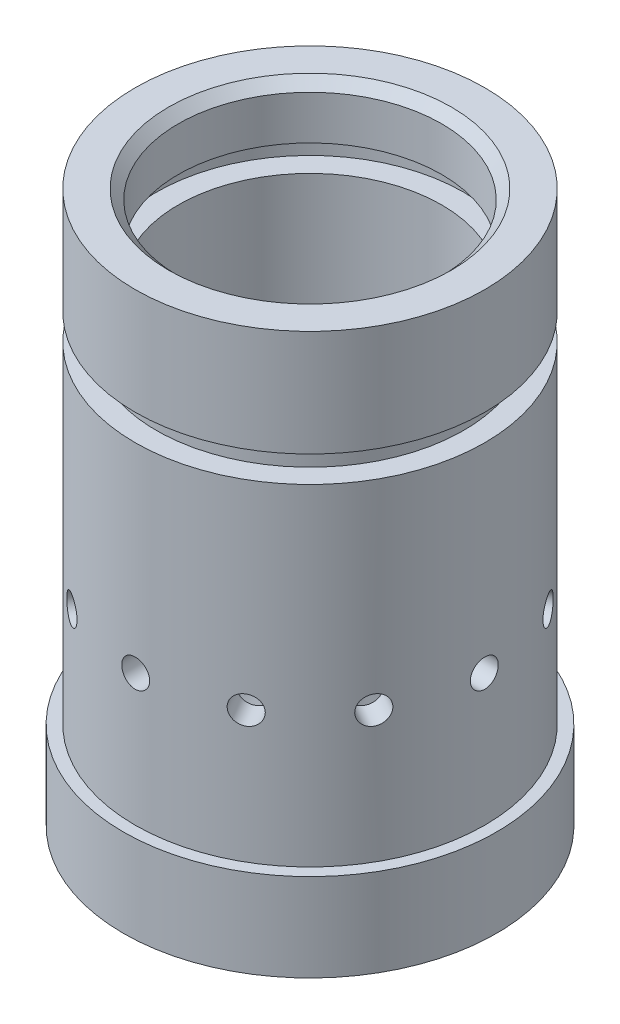
SolidWorks part; units mm, degrees
material "6061 Alloy"
ref_plane "Front Plane" through (0, 0, 0) normal (0, 0, 1) x (1, 0, 0)
ref_plane "Top Plane" through (0, 0, 0) normal (0, 1, 0) x (1, 0, 0)
ref_plane "Right Plane" through (0, 0, 0) normal (1, 0, 0) x (0, 0, -1)
sketch "Sketch1" plane through (0, 0, 0) normal (0, 0, 1) x (1, 0, 0)
  line L0 (0, 0) -> (0, 10.9165) construction
  line L1 (19.05, -48.1471) -> (19.05, -6.4911)
  line L2 (19.05, -6.4911) -> (20.447, -5.0941)
  line L3 (20.447, -5.0941) -> (25.2857, -5.0941)
  line L6 (25.2857, -5.0941) -> (25.2857, -48.1471)
  line L7 (25.2857, -48.1471) -> (19.05, -48.1471)
  line L8 (19.05, -48.1471) -> (15.875, -48.1471)
  line L9 (15.875, -48.1471) -> (25.7175, -84.8798)
  line L11 (25.7175, -84.8798) -> (26.9875, -84.8798)
  line L13 (15.875, -48.1471) -> (7.9375, -18.5239) construction
  line L14 (26.9875, -72.1798) -> (26.9875, -84.8798)
  line L15 (25.2857, -48.1471) -> (25.2857, -72.1798)
  line L16 (-26.9875, -72.1798) -> (26.9875, -72.1798) construction
  line L17 (25.2857, -72.1798) -> (26.9875, -72.1798)
  line L18 (-26.9875, -72.1798) -> (-26.9875, -84.8798)
  line L19 (-26.9875, -84.8798) -> (26.9875, -84.8798) construction
  line L20 (-22.2123, -5.0941) -> (22.2123, -5.0941) construction
  line L21 (19.05, -12.8411) -> (22.225, -12.8411)
  line L22 (25.2857, -20.4611) -> (22.225, -20.4611)
  line L23 (25.2857, -20.4611) -> (25.2857, -24.2711)
  line L24 (25.2857, -24.2711) -> (22.225, -24.2711)
  line L25 (22.225, -20.4611) -> (22.225, -24.2711)
  line L26 (19.05, -12.8411) -> (19.05, -16.6511)
  line L27 (19.05, -16.6511) -> (22.225, -16.6511)
  line L28 (22.225, -12.8411) -> (22.225, -16.6511)
  line L29 (-25.7175, -84.8798) -> (-26.9875, -84.8798)
  line L30 (-15.875, -48.1471) -> (-25.7175, -84.8798)
  line L31 (-22.225, -12.8411) -> (-22.225, -16.6511)
  line L32 (-19.05, -16.6511) -> (-22.225, -16.6511)
  line L33 (-19.05, -12.8411) -> (-19.05, -16.6511)
  line L34 (-22.225, -20.4611) -> (-22.225, -24.2711)
  line L35 (-25.2857, -24.2711) -> (-22.225, -24.2711)
  line L36 (-25.2857, -20.4611) -> (-25.2857, -24.2711)
  line L37 (-25.2857, -20.4611) -> (-22.225, -20.4611)
  line L38 (-19.05, -12.8411) -> (-22.225, -12.8411)
  line L39 (-25.2857, -72.1798) -> (-26.9875, -72.1798)
  line L40 (-25.2857, -48.1471) -> (-25.2857, -72.1798)
  line L41 (-19.05, -48.1471) -> (-15.875, -48.1471)
  line L42 (-25.2857, -48.1471) -> (-19.05, -48.1471)
  line L43 (-25.2857, -5.0941) -> (-25.2857, -48.1471)
  line L44 (-20.447, -5.0941) -> (-25.2857, -5.0941)
  line L45 (-19.05, -6.4911) -> (-20.447, -5.0941)
  line L46 (-19.05, -48.1471) -> (-19.05, -6.4911)
  point P26 (25.2857, -5.0941)
  point P37 (15.875, -48.1471)
  point P53 (-15.875, -48.1471)
  point P54 (-25.2857, -5.0941)
  dimension "D1" = 44.45
  dimension "D2" = 3.81
  dimension "D3" = 44.45
  dimension "D4" = 3.81
  dimension "D5" = 19.05
  dimension "D6" = 45
  dimension "D7" = 1.397
  dimension "D8" = 3.0607
  dimension "D9" = 6.35
revolve "Revolve1" add sketch "Sketch1" angle 360 about L0 region at (22.1785, -27.4978, 0) region at (22.6048, -61.9724, 0)
ref_plane "Plane1" through (0, 0, -25.2857) normal (0, 0, -1) x (-1, 0, 0)
sketch "Sketch2" plane through (0, 0, -25.2857) normal (0, 0, -1) x (-1, 0, 0)
  point P0 (0, -53.1298)
hole_wizard "#10-32 Tapped Hole1" positions "Sketch2" profile "Sketch3" tap size "#10-32" standard "ANSI Inch"
sketch "Sketch3" plane through (0, -53.1298, -25.2857) normal (1, 0, 0) x (0, 1, 0)
  line L0 (0, 0) -> (0, 4.1661)
  line L1 (0, 4.1661) -> (2.0193, 3.81)
  line L2 (2.0193, 3.81) -> (2.0193, 0)
  line L5 (2.0193, 0) -> (0, 0)
  line L10 (0, 4.1661) -> (-2.0193, 3.81) construction
  line L11 (0, -6.35) -> (0, 107.95) construction
  dimension "Tap Drill Dia." = 4.0386
  dimension "Tap Drill Depth" = 3.81
  dimension "Drill Angle" = 160
pattern_circular "CirPattern1" count 12 over 360 about axis through (0, 0, 0) along (0, -1, 0) of "#10-32 Tapped Hole1" reverse direction yes
